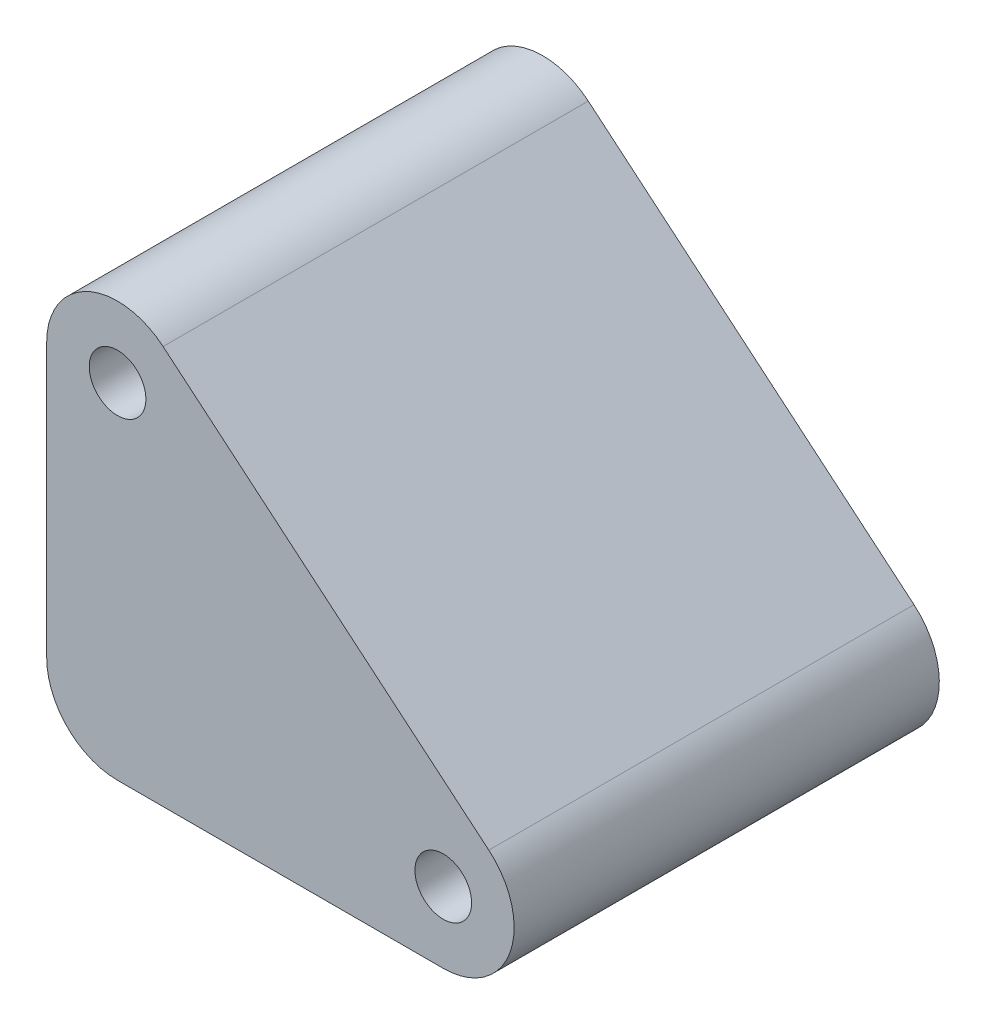
SolidWorks part; units mm, degrees
ref_plane "Front Plane" through (0, 0, 0) normal (0, 0, 1) x (1, 0, 0)
ref_plane "Top Plane" through (0, 0, 0) normal (0, 1, 0) x (1, 0, 0)
ref_plane "Right Plane" through (0, 0, 0) normal (1, 0, 0) x (0, 0, -1)
sketch "Sketch1" plane through (0, 0, 0) normal (0, 0, 1) x (1, 0, 0)
  line L3 (-261.5046, 29.7013) -> (-238.5233, 10.4177) construction
  line L4 (-241.7372, 1.5874) -> (-264.7185, 1.5874) construction
  line L5 (-269.7185, 6.5874) -> (-269.7185, 25.8711) construction
  line L6 (-261.5046, 29.7013) -> (-238.5233, 10.4177)
  line L7 (-241.7372, 1.5874) -> (-264.7185, 1.5874)
  line L8 (-269.7185, 6.5874) -> (-269.7185, 25.8711)
  circle A7 centre (-264.7185, 25.8711) radius 2 construction
  circle A8 centre (-241.7372, 6.5874) radius 2 construction
  arc A9 (-241.7372, 1.5874) -> (-238.5233, 10.4177) centre (-241.7372, 6.5874) ccw construction
  arc A10 (-269.7185, 6.5874) -> (-264.7185, 1.5874) centre (-264.7185, 6.5874) ccw construction
  arc A11 (-261.5046, 29.7013) -> (-269.7185, 25.8711) centre (-264.7185, 25.8711) ccw construction
  circle A12 centre (-264.7185, 25.8711) radius 2
  circle A13 centre (-241.7372, 6.5874) radius 2
  arc A14 (-241.7372, 1.5874) -> (-238.5233, 10.4177) centre (-241.7372, 6.5874) ccw
  arc A15 (-269.7185, 6.5874) -> (-264.7185, 1.5874) centre (-264.7185, 6.5874) ccw
  arc A16 (-261.5046, 29.7013) -> (-269.7185, 25.8711) centre (-264.7185, 25.8711) ccw
  point P0 (0, 0)
extrude "Boss-Extrude1" add sketch "Sketch1" along normal blind 15 and the other way blind 15
